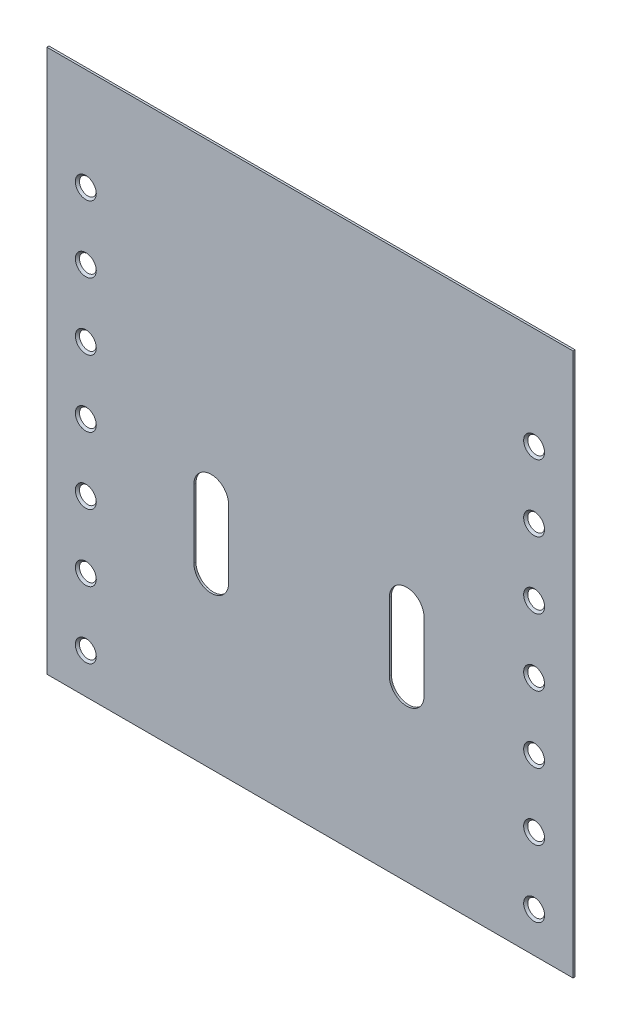
SolidWorks part; units mm, degrees
ref_plane "Front Plane" through (0, 0, 0) normal (0, 0, 1) x (1, 0, 0)
ref_plane "Top Plane" through (0, 0, 0) normal (0, 1, 0) x (1, 0, 0)
ref_plane "Right Plane" through (0, 0, 0) normal (1, 0, 0) x (0, 0, -1)
sketch "Sketch1" plane through (0, 0, 0) normal (0, 0, -1) x (1, 0, 0)
  line L1 (-203.2, 237) -> (-6.35, 237)
  line L2 (-203.2, 237) -> (-203.2, 33.8)
  line L3 (-203.2, 33.8) -> (-6.35, 33.8)
  line L4 (-6.35, 237) -> (-6.35, 33.8)
  dimension "D2" = 196.85
  dimension "D3" = 203.2
extrude "Boss-Extrude1" add sketch "Sketch1" along normal blind 0.7747
sketch "Sketch2" plane through (0, 0, -0.7747) normal (0, 0, -1) x (1, 0, 0)
  line L0 (-141.7213, 180) -> (-141.7213, 141.5) construction
  line L1 (-6.35, 237) -> (-203.2, 237) construction
  line L2 (-141.7213, 180) -> (-141.7213, 237) construction
  line L3 (-141.7213, 173.5) -> (-141.7213, 148) construction
  line L6 (-135.2213, 173.5) -> (-135.2213, 148)
  line L7 (-148.2213, 173.5) -> (-148.2213, 148)
  line L8 (-141.7213, 160.75) -> (-203.2, 160.75) construction
  line L9 (-203.2, 237) -> (-203.2, 33.8) construction
  line L10 (-68.5693, 180) -> (-68.5693, 141.5) construction
  line L11 (-68.5693, 180) -> (-68.5693, 237) construction
  line L12 (-68.5693, 173.5) -> (-68.5693, 148) construction
  line L15 (-141.7213, 160.75) -> (-68.5693, 160.75) construction
  line L16 (-62.0693, 173.5) -> (-62.0693, 148)
  line L17 (-75.0693, 173.5) -> (-75.0693, 148)
  arc A2 (-135.2213, 173.5) -> (-148.2213, 173.5) centre (-141.7213, 173.5) ccw
  arc A3 (-148.2213, 148) -> (-135.2213, 148) centre (-141.7213, 148) ccw
  arc A6 (-62.0693, 173.5) -> (-75.0693, 173.5) centre (-68.5693, 173.5) ccw
  arc A7 (-75.0693, 148) -> (-62.0693, 148) centre (-68.5693, 148) ccw
  point P0 (-141.7213, 160.75)
  point P5 (-141.7213, 160.75)
  point P18 (-68.5693, 160.75)
  dimension "D4" = 6.5
  dimension "D6" = 57
  dimension "D5" = 6.5
  dimension "D1" = 73.152
  dimension "D2" = 57
  dimension "D3" = 38.5
  dimension "D8" = 38.5
extrude "Cut-Extrude7" cut sketch "Sketch2" against normal through all
ref_plane "Plane1" through (-104.775, 0, 0) normal (1, 0, 0) x (0, 0, -1)
sketch "Sketch4" plane through (0, 0, 0) normal (0, 0, 1) x (1, 0, 0)
  line L0 (-203.2, -33.8) -> (-6.35, -33.8) construction
  line L1 (-6.35, -33.8) -> (-203.2, -33.8)
  line L2 (-6.35, -33.8) -> (-6.35, -34.4096)
  line L3 (-6.35, -34.4096) -> (-203.2, -34.4096)
  line L4 (-203.2, -33.8) -> (-203.2, -34.4096)
  line L5 (-6.35, -237) -> (-6.35, 2) construction
  line L6 (-203.2, 2) -> (-203.2, -237) construction
  dimension "D1" = 0.6096
extrude "Boss-Extrude2" add sketch "Sketch4" along normal blind 12
sketch "Sketch8" plane through (0, 0, -0.7747) normal (0, 0, -1) x (-1, 0, 0)
  circle A0 centre (185.47, -222) radius 3.75
  circle A1 centre (185.47, -197) radius 3.75
  circle A2 centre (185.47, -172) radius 3.75
  circle A3 centre (185.47, -147) radius 3.75
  circle A4 centre (185.47, -122) radius 3.75
  circle A5 centre (185.47, -97) radius 3.75
  dimension "D1" = 7.5
sketch "Sketch13" plane through (0, 0, 12) normal (0, 0, 1) x (1, 0, 0)
  line L1 (-6.35, -34.4096) -> (-203.2, -34.4096)
  line L2 (-6.35, -34.4096) -> (-6.35, -33.8)
  line L3 (-6.35, -33.8) -> (-203.2, -33.8)
  line L4 (-203.2, -34.4096) -> (-203.2, -33.8)
sketch "Sketch14" plane through (0, 0, 0) normal (0, 0, 1) x (1, 0, 0)
  line L0 (-6.35, -34.4096) -> (-6.35, -237) construction
  line L1 (-6.35, -59.904) -> (-203.2, -59.904)
  line L2 (-6.35, -59.904) -> (-6.35, -47.966)
  line L3 (-6.35, -47.966) -> (-203.2, -47.966)
  line L4 (-203.2, -59.904) -> (-203.2, -47.966)
  line L5 (-203.2, -237) -> (-203.2, -34.4096) construction
  dimension "D1" = 11.938
extrude "Boss-Extrude3" add sketch "Sketch14" against normal up to surface (0.7747 mm away) up to face at (-141.7213, -160.75, -0.7747)
extrude "Cut-Extrude9" cut sketch "Sketch13" against normal up to surface (12 mm away) up to face at (-68.5693, -160.75, 0)
hole_wizard "CSK for M3 Flat Head Machine Screw3" positions "Sketch15" profile "Sketch16" countersink size "M3" standard "ANSI Metric" end condition through all
sketch "Sketch15" plane through (0, 0, 0) normal (0, 0, 1) x (1, 0, 0)
  point P18 (-188.645, -72)
  point P21 (-188.645, -222)
  point P24 (-188.645, -197)
  point P27 (-188.645, -172)
  point P30 (-188.645, -147)
  point P33 (-188.645, -122)
  point P36 (-188.645, -97)
  point P39 (-188.645, -72)
sketch "Sketch16" plane through (-188.645, -72, 0) normal (1, 0, 0) x (0, -1, 0)
  line L0 (0, 0) -> (0, 0.7747)
  line L1 (0, 0.7747) -> (1.7, 0.7747)
  line L2 (1.7, 0.7747) -> (1.7, 2.212)
  line L3 (1.7, 2.212) -> (3.912, 0)
  line L5 (3.912, 0) -> (0, 0)
  line L6 (-1.7, 2.212) -> (-3.912, 0) construction
  line L11 (0, -6.35) -> (0, 107.95) construction
  dimension "Thru Hole Dia." = 3.4
  dimension "Thru Hole Depth" = 0.7747
  dimension "Near C'Sink Dia." = 7.824
  dimension "Near C'Sink Angle" = 90
ref_plane "Plane2" through (-104.775, 0, 0) normal (-1, 0, 0) x (0, 0, 1)
mirror "Mirror1" about plane through (-104.775, 0, 0) normal (-1, 0, 0) of "CSK for M3 Flat Head Machine Screw3"
